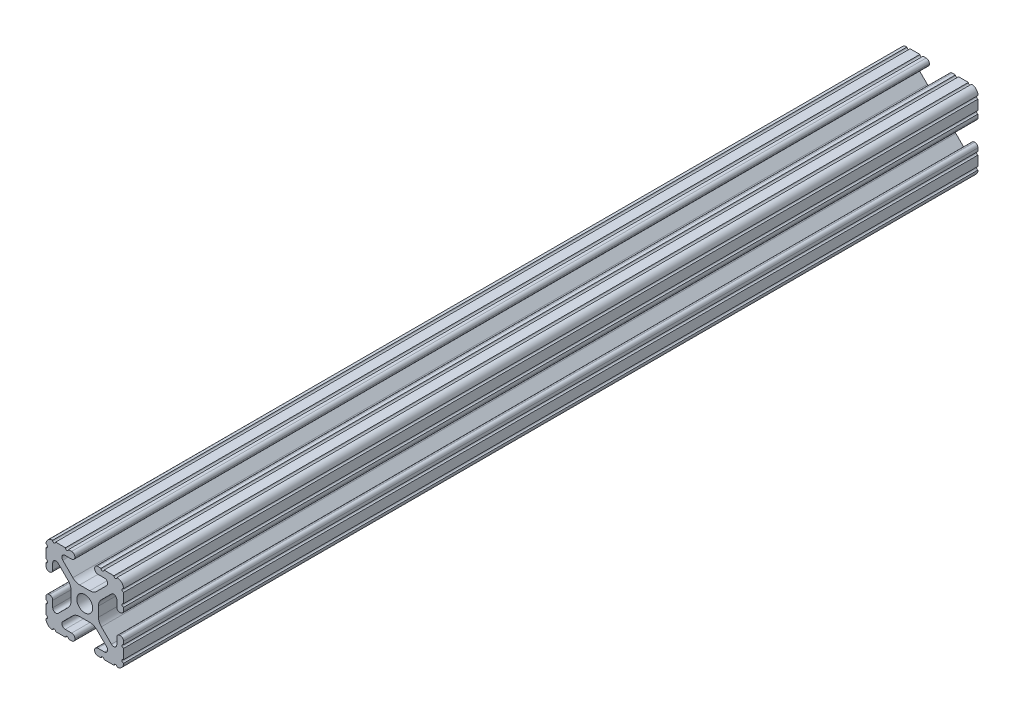
SolidWorks part; units mm, degrees
material "6105-T5 Aluminum"
ref_plane "Front Plane" through (0, 0, 0) normal (0, 0, 1) x (1, 0, 0)
ref_plane "Top Plane" through (0, 0, 0) normal (0, 1, 0) x (1, 0, 0)
ref_plane "Right Plane" through (0, 0, 0) normal (1, 0, 0) x (0, 0, -1)
sketch "Sketch1" plane through (0, 0, 0) normal (0, 0, 1) x (1, 0, 0)
  line L0 (-7.207, 8.7244) -> (-3.8983, 5.4232)
  line L1 (-4.2875, 10.4902) -> (-6.4768, 10.4902)
  line L2 (-3.2385, 11.651) -> (-3.2385, 11.5392)
  line L3 (-5.3171, 12.7) -> (-4.2875, 12.7)
  line L4 (0, 13.4005) -> (0, -14.8534) construction
  line L5 (12.7, 0) -> (-13.9989, 0) construction
  line L6 (-9.5504, 12.7) -> (-6.3331, 12.7)
  line L7 (-12.7, 6.3331) -> (-12.7, 9.5504)
  line L8 (-12.7, 4.2875) -> (-12.7, 5.3171)
  line L9 (-11.5392, 3.2385) -> (-11.651, 3.2385)
  line L10 (-10.4902, 6.4021) -> (-10.4902, 4.2875)
  line L11 (-5.441, 3.8408) -> (-8.7371, 7.1294)
  line L12 (-4.5085, -1.5932) -> (-4.5085, 1.5932)
  line L13 (-1.7093, -4.4958) -> (1.7093, -4.4958)
  line L14 (3.9523, -5.4237) -> (7.1797, -8.6452)
  line L15 (6.4164, -10.4902) -> (4.2875, -10.4902)
  line L16 (3.2385, -11.5392) -> (3.2385, -11.651)
  line L17 (4.2875, -12.7) -> (5.3171, -12.7)
  line L18 (6.3331, -12.7) -> (9.5504, -12.7)
  line L19 (12.7, -9.5504) -> (12.7, -6.3331)
  line L20 (12.7, -5.3171) -> (12.7, -4.2875)
  line L21 (11.651, -3.2385) -> (11.5392, -3.2385)
  line L22 (10.4902, -4.2875) -> (10.4902, -6.4021)
  line L23 (8.7371, -7.1294) -> (5.441, -3.8408)
  line L24 (4.5085, -1.5932) -> (4.5085, 1.5932)
  line L25 (5.441, 3.8408) -> (8.7371, 7.1294)
  line L26 (10.4902, 6.4021) -> (10.4902, 4.2875)
  line L27 (11.5392, 3.2385) -> (11.651, 3.2385)
  line L28 (12.7, 4.2875) -> (12.7, 5.3171)
  line L29 (12.7, 6.3331) -> (12.7, 9.5504)
  line L30 (9.5504, 12.7) -> (6.3331, 12.7)
  line L31 (5.3171, 12.7) -> (4.2875, 12.7)
  line L32 (3.2385, 11.651) -> (3.2385, 11.5392)
  line L33 (4.2875, 10.4902) -> (6.4768, 10.4902)
  line L34 (7.207, 8.7244) -> (3.8983, 5.4232)
  line L35 (1.6558, 4.4958) -> (-1.6558, 4.4958)
  line L36 (-8.7371, -7.1294) -> (-5.441, -3.8408)
  line L37 (-10.4902, -4.2875) -> (-10.4902, -6.4021)
  line L38 (-11.651, -3.2385) -> (-11.5392, -3.2385)
  line L39 (-12.7, -5.3171) -> (-12.7, -4.2875)
  line L40 (-12.7, -9.5504) -> (-12.7, -6.3331)
  line L41 (-6.3331, -12.7) -> (-9.5504, -12.7)
  line L42 (-4.2875, -12.7) -> (-5.3171, -12.7)
  line L43 (-3.2385, -11.5392) -> (-3.2385, -11.651)
  line L44 (-6.4164, -10.4902) -> (-4.2875, -10.4902)
  line L45 (-3.9523, -5.4237) -> (-7.1797, -8.6452)
  arc A0 (-7.207, 8.7244) -> (-6.4768, 10.4902) centre (-6.4768, 9.4563) cw
  arc A1 (-3.2385, 11.5392) -> (-4.2875, 10.4902) centre (-4.2875, 11.5392) cw
  arc A2 (-4.2875, 12.7) -> (-3.2385, 11.651) centre (-4.2875, 11.651) cw
  arc A3 (-5.3171, 12.7) -> (-6.3331, 12.7) centre (-5.8251, 12.7) cw
  arc A4 (-9.5504, 12.7) -> (-10.5664, 12.6998) centre (-10.0584, 12.7) cw
  arc A5 (-12.6998, 10.5664) -> (-10.5664, 12.6998) centre (-10.5918, 10.5918) cw
  arc A6 (-12.6998, 10.5664) -> (-12.7, 9.5504) centre (-12.7, 10.0584) cw
  arc A7 (-12.7, 6.3331) -> (-12.7, 5.3171) centre (-12.7, 5.8251) cw
  arc A8 (-11.651, 3.2385) -> (-12.7, 4.2875) centre (-11.651, 4.2875) cw
  arc A9 (-10.4902, 4.2875) -> (-11.5392, 3.2385) centre (-11.5392, 4.2875) cw
  circle A10 centre (0, 0) radius 2.6035
  arc A11 (-10.4902, 6.4021) -> (-8.7371, 7.1294) centre (-9.4628, 6.4021) cw
  arc A12 (-5.441, 3.8408) -> (-4.5085, 1.5932) centre (-7.6835, 1.5932) cw
  arc A13 (-4.5085, -1.5932) -> (-5.441, -3.8408) centre (-7.6835, -1.5932) cw
  arc A14 (-8.7371, -7.1294) -> (-10.4902, -6.4021) centre (-9.4628, -6.4021) cw
  arc A15 (-1.7093, -4.4958) -> (-3.9523, -5.4237) centre (-1.7093, -7.6708) ccw
  arc A16 (3.9523, -5.4237) -> (1.7093, -4.4958) centre (1.7093, -7.6708) ccw
  arc A17 (6.4164, -10.4902) -> (7.1797, -8.6452) centre (6.4164, -9.4098) ccw
  arc A18 (4.2875, -10.4902) -> (3.2385, -11.5392) centre (4.2875, -11.5392) ccw
  arc A19 (3.2385, -11.651) -> (4.2875, -12.7) centre (4.2875, -11.651) ccw
  arc A20 (6.3331, -12.7) -> (5.3171, -12.7) centre (5.8251, -12.7) ccw
  arc A21 (10.5664, -12.6998) -> (9.5504, -12.7) centre (10.0584, -12.7) ccw
  arc A22 (10.5664, -12.6998) -> (12.6998, -10.5664) centre (10.5918, -10.5918) ccw
  arc A23 (12.7, -9.5504) -> (12.6998, -10.5664) centre (12.7, -10.0584) ccw
  arc A24 (12.7, -5.3171) -> (12.7, -6.3331) centre (12.7, -5.8251) ccw
  arc A25 (12.7, -4.2875) -> (11.651, -3.2385) centre (11.651, -4.2875) ccw
  arc A26 (11.5392, -3.2385) -> (10.4902, -4.2875) centre (11.5392, -4.2875) ccw
  arc A27 (8.7371, -7.1294) -> (10.4902, -6.4021) centre (9.4628, -6.4021) ccw
  arc A28 (4.5085, -1.5932) -> (5.441, -3.8408) centre (7.6835, -1.5932) ccw
  arc A29 (5.441, 3.8408) -> (4.5085, 1.5932) centre (7.6835, 1.5932) ccw
  arc A30 (10.4902, 6.4021) -> (8.7371, 7.1294) centre (9.4628, 6.4021) ccw
  arc A31 (10.4902, 4.2875) -> (11.5392, 3.2385) centre (11.5392, 4.2875) ccw
  arc A32 (11.651, 3.2385) -> (12.7, 4.2875) centre (11.651, 4.2875) ccw
  arc A33 (12.7, 6.3331) -> (12.7, 5.3171) centre (12.7, 5.8251) ccw
  arc A34 (12.6998, 10.5664) -> (12.7, 9.5504) centre (12.7, 10.0584) ccw
  arc A35 (12.6998, 10.5664) -> (10.5664, 12.6998) centre (10.5918, 10.5918) ccw
  arc A36 (9.5504, 12.7) -> (10.5664, 12.6998) centre (10.0584, 12.7) ccw
  arc A37 (5.3171, 12.7) -> (6.3331, 12.7) centre (5.8251, 12.7) ccw
  arc A38 (4.2875, 12.7) -> (3.2385, 11.651) centre (4.2875, 11.651) ccw
  arc A39 (3.2385, 11.5392) -> (4.2875, 10.4902) centre (4.2875, 11.5392) ccw
  arc A40 (7.207, 8.7244) -> (6.4768, 10.4902) centre (6.4768, 9.4563) ccw
  arc A41 (1.6558, 4.4958) -> (3.8983, 5.4232) centre (1.6558, 7.6708) ccw
  arc A42 (-1.6558, 4.4958) -> (-3.8983, 5.4232) centre (-1.6558, 7.6708) cw
  arc A43 (-11.5392, -3.2385) -> (-10.4902, -4.2875) centre (-11.5392, -4.2875) cw
  arc A44 (-12.7, -4.2875) -> (-11.651, -3.2385) centre (-11.651, -4.2875) cw
  arc A45 (-12.7, -5.3171) -> (-12.7, -6.3331) centre (-12.7, -5.8251) cw
  arc A46 (-12.7, -9.5504) -> (-12.6998, -10.5664) centre (-12.7, -10.0584) cw
  arc A47 (-10.5664, -12.6998) -> (-12.6998, -10.5664) centre (-10.5918, -10.5918) cw
  arc A48 (-10.5664, -12.6998) -> (-9.5504, -12.7) centre (-10.0584, -12.7) cw
  arc A49 (-6.3331, -12.7) -> (-5.3171, -12.7) centre (-5.8251, -12.7) cw
  arc A50 (-3.2385, -11.651) -> (-4.2875, -12.7) centre (-4.2875, -11.651) cw
  arc A51 (-4.2875, -10.4902) -> (-3.2385, -11.5392) centre (-4.2875, -11.5392) cw
  arc A52 (-6.4164, -10.4902) -> (-7.1797, -8.6452) centre (-6.4164, -9.4098) cw
  dimension "D1" = 5.207
  dimension "D9" = 14.859
  dimension "D2" = 25.4
  dimension "D3" = 12.7
  dimension "D4" = 6.477
  dimension "D5" = 8.2042
  dimension "D6" = 9.017
  dimension "D8" = 2.2098
  dimension "D10" = 2.2098
extrude "Extrude1" add sketch "Sketch1" against normal mid plane 280
